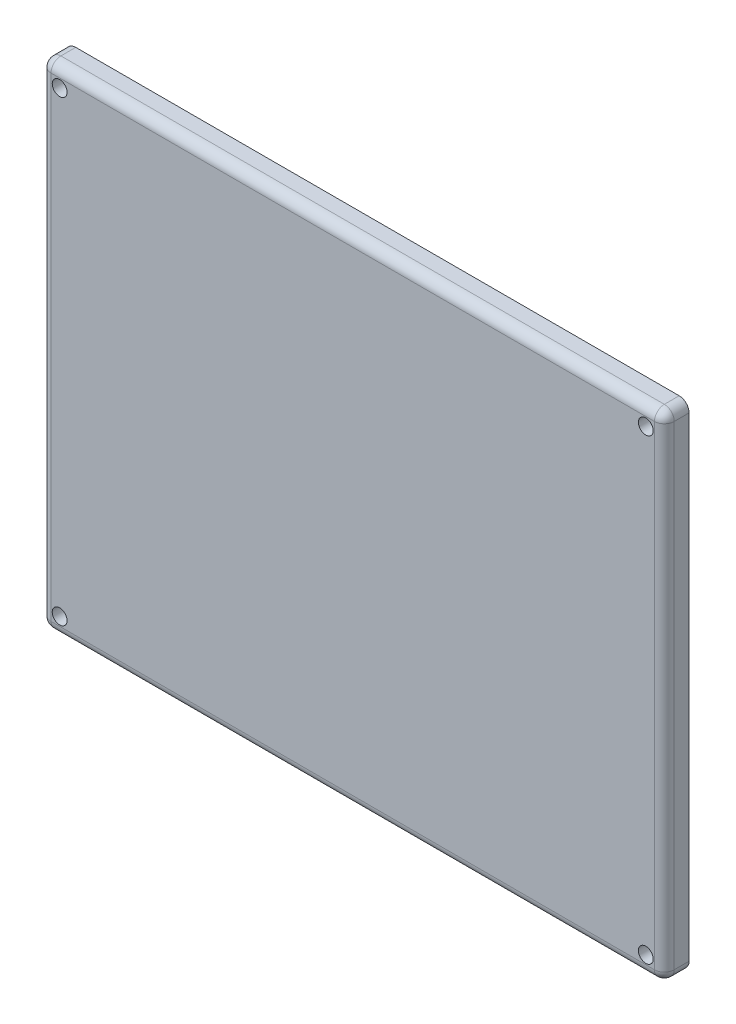
SolidWorks part; units mm, degrees
ref_plane "Front Plane" through (0, 0, 0) normal (0, 0, 1) x (1, 0, 0)
ref_plane "Top Plane" through (0, 0, 0) normal (0, 1, 0) x (1, 0, 0)
ref_plane "Right Plane" through (0, 0, 0) normal (1, 0, 0) x (0, 0, -1)
sketch "Sketch1" plane through (0, 0, 0) normal (0, 0, 1) x (1, 0, 0)
  line L1 (0, 0) -> (160.02, 0)
  line L2 (0, 0) -> (0, -127)
  line L3 (0, -127) -> (160.02, -127)
  line L4 (160.02, 0) -> (160.02, -127)
  dimension "D1" = 160.02
  dimension "D2" = 127
extrude "Boss-Extrude1" add sketch "Sketch1" along normal blind 6.35
fillet "Fillet1" radius 2.54 8 edges at (80.01, 0, 6.35) (160.02, -63.5, 6.35) (80.01, -127, 6.35) (0, -63.5, 6.35) (0, -127, 3.175) (160.02, -127, 3.175) (0, 0, 3.175) (160.02, 0, 3.175)
shell "Shell1" thickness 2.54 removed face at (80.01, -63.5, 0)
chamfer "Chamfer1" distance 10.16 angle 45 4 edges at (157.48, -124.46, 1.905) (2.54, -124.46, 1.905) (2.54, -2.54, 1.905) (157.48, -2.54, 1.905)
hole_wizard "9/64 (0.15) Diameter Hole1" positions "Sketch3" profile "Sketch4" hole size "9/64" standard "ANSI Inch"
sketch "Sketch3" plane through (0, 0, 0) normal (0, 0, -1) x (-1, 0, 0)
  line L4 (-157.48, 0) -> (-2.54, 0) construction
  line L5 (0, -2.54) -> (0, -124.46) construction
  line L6 (-2.54, -127) -> (-157.48, -127) construction
  line L7 (-160.02, -124.46) -> (-160.02, -2.54) construction
  point P0 (-155.2575, -4.7625)
  point P2 (-4.7625, -4.7625)
  point P4 (-4.7625, -122.2375)
  point P6 (-155.2575, -122.2375)
  dimension "D1" = 4.7625
  dimension "D2" = 4.7625
  dimension "D3" = 4.7625
  dimension "D4" = 4.7625
sketch "Sketch4" plane through (155.2575, -4.7625, 0) normal (1, 0, 0) x (0, 1, 0)
  line L0 (0, 0) -> (0, 7.4946)
  line L1 (0, 7.4946) -> (1.905, 6.35)
  line L2 (1.905, 6.35) -> (1.905, 0)
  line L5 (1.905, 0) -> (0, 0)
  line L10 (0, 7.4946) -> (-1.905, 6.35) construction
  line L11 (0, -6.35) -> (0, 107.95) construction
  dimension "Hole Dia." = 3.81
  dimension "Hole Depth" = 6.35
  dimension "Drill Angle" = 118
